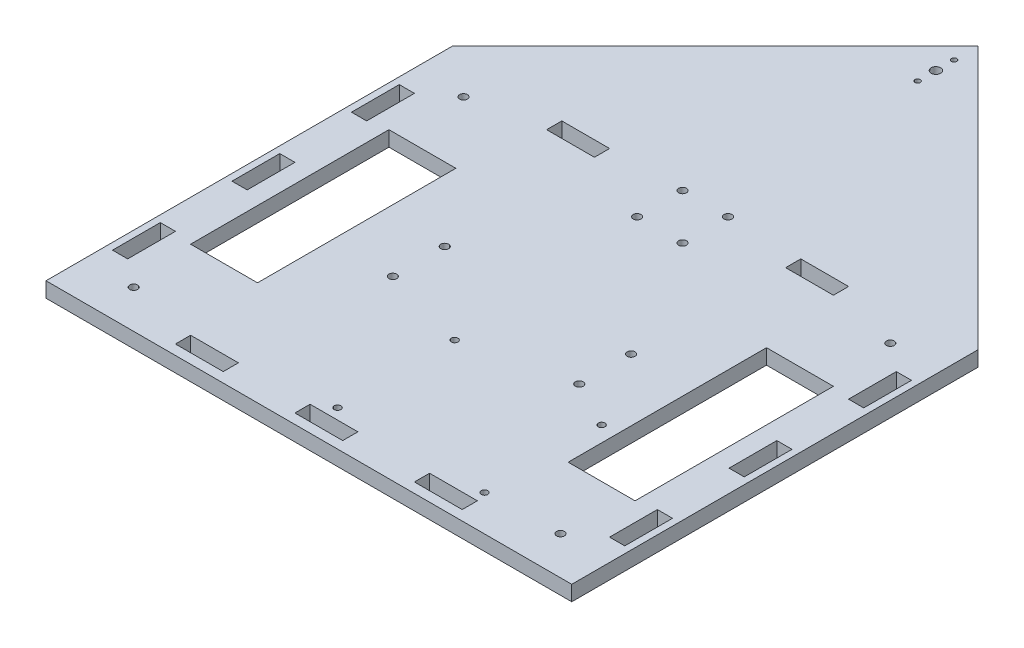
SolidWorks part; units mm, degrees
ref_plane "Front Plane" through (0, 0, 0) normal (0, 0, 1) x (1, 0, 0)
ref_plane "Top Plane" through (0, 0, 0) normal (0, 1, 0) x (1, 0, 0)
ref_plane "Right Plane" through (0, 0, 0) normal (1, 0, 0) x (0, 0, -1)
sketch "Sketch1" plane through (0, 0, 0) normal (0, 1, 0) x (1, 0, 0)
  line L0 (-110, 85) -> (0, 195)
  line L1 (-110, 85) -> (110, 85) construction
  line L2 (-110, 85) -> (-110, -85)
  line L3 (-110, -85) -> (110, -85)
  line L4 (110, 85) -> (110, -85)
  line L5 (-110, 85) -> (110, -85) construction
  line L6 (-110, -85) -> (110, 85) construction
  line L7 (0, 195) -> (110, 85)
  line L8 (0, 85) -> (0, -85) construction
  line L9 (-93, 41.5) -> (-65, 41.5)
  line L10 (-93, 41.5) -> (-93, -41.5)
  line L11 (-93, -41.5) -> (-65, -41.5)
  line L12 (-65, 41.5) -> (-65, -41.5)
  line L13 (-93, 41.5) -> (-65, -41.5) construction
  line L14 (-93, -41.5) -> (-65, 41.5) construction
  line L15 (-110, 0) -> (110, 0) construction
  line L16 (-107.175, 60) -> (-100.825, 60)
  line L17 (-107.175, 10) -> (-100.825, 10)
  line L18 (-107.175, 10) -> (-107.175, -10)
  line L19 (-107.175, -10) -> (-100.825, -10)
  line L20 (-100.825, 10) -> (-100.825, -10)
  line L21 (-107.175, 10) -> (-100.825, -10) construction
  line L22 (-107.175, -10) -> (-100.825, 10) construction
  line L23 (-107.175, 60) -> (-107.175, 40)
  line L24 (-107.175, 40) -> (-100.825, 40)
  line L25 (-100.825, 60) -> (-100.825, 40)
  line L26 (-107.175, 60) -> (-100.825, 40) construction
  line L27 (-107.175, 40) -> (-100.825, 60) construction
  line L28 (-107.175, -40) -> (-100.825, -40)
  line L29 (-107.175, -40) -> (-107.175, -60)
  line L30 (-107.175, -60) -> (-100.825, -60)
  line L31 (-100.825, -40) -> (-100.825, -60)
  line L32 (-107.175, -40) -> (-100.825, -60) construction
  line L33 (-107.175, -60) -> (-100.825, -40) construction
  line L34 (40, -74.4921) -> (60, -74.4921)
  line L35 (-10, -74.4921) -> (10, -74.4921)
  line L36 (-10, -74.4921) -> (-10, -80.8421)
  line L37 (-10, -80.8421) -> (10, -80.8421)
  line L38 (10, -74.4921) -> (10, -80.8421)
  line L39 (-10, -74.4921) -> (10, -80.8421) construction
  line L40 (-10, -80.8421) -> (10, -74.4921) construction
  line L41 (40, -74.4921) -> (40, -80.8421)
  line L42 (40, -80.8421) -> (60, -80.8421)
  line L43 (60, -74.4921) -> (60, -80.8421)
  line L44 (40, -74.4921) -> (60, -80.8421) construction
  line L45 (40, -80.8421) -> (60, -74.4921) construction
  line L46 (-60, -74.4921) -> (-40, -74.4921)
  line L47 (-60, -74.4921) -> (-60, -80.8421)
  line L48 (-60, -80.8421) -> (-40, -80.8421)
  line L49 (-40, -74.4921) -> (-40, -80.8421)
  line L50 (-60, -74.4921) -> (-40, -80.8421) construction
  line L51 (-60, -80.8421) -> (-40, -74.4921) construction
  line L52 (107.175, -60) -> (100.825, -40) construction
  line L53 (107.175, -40) -> (100.825, -60) construction
  line L54 (107.175, 40) -> (100.825, 60) construction
  line L55 (107.175, 60) -> (100.825, 40) construction
  line L56 (107.175, -10) -> (100.825, 10) construction
  line L57 (107.175, 10) -> (100.825, -10) construction
  line L58 (100.825, -40) -> (100.825, -60)
  line L59 (107.175, -60) -> (100.825, -60)
  line L60 (107.175, -40) -> (107.175, -60)
  line L61 (107.175, -40) -> (100.825, -40)
  line L62 (100.825, 60) -> (100.825, 40)
  line L63 (107.175, 40) -> (100.825, 40)
  line L64 (107.175, 60) -> (107.175, 40)
  line L65 (100.825, 10) -> (100.825, -10)
  line L66 (107.175, -10) -> (100.825, -10)
  line L67 (107.175, 10) -> (107.175, -10)
  line L68 (107.175, 10) -> (100.825, 10)
  line L69 (107.175, 60) -> (100.825, 60)
  line L70 (-60, 80.8421) -> (-40, 74.4921) construction
  line L71 (-60, 74.4921) -> (-40, 80.8421) construction
  line L72 (40, 80.8421) -> (60, 74.4921) construction
  line L73 (40, 74.4921) -> (60, 80.8421) construction
  line L76 (-40, 74.4921) -> (-40, 80.8421)
  line L77 (-60, 80.8421) -> (-40, 80.8421)
  line L78 (-60, 74.4921) -> (-60, 80.8421)
  line L79 (-60, 74.4921) -> (-40, 74.4921)
  line L80 (60, 74.4921) -> (60, 80.8421)
  line L81 (40, 80.8421) -> (60, 80.8421)
  line L82 (40, 74.4921) -> (40, 80.8421)
  line L87 (40, 74.4921) -> (60, 74.4921)
  line L88 (93, -41.5) -> (65, 41.5) construction
  line L89 (93, 41.5) -> (65, -41.5) construction
  line L90 (65, 41.5) -> (65, -41.5)
  line L91 (93, -41.5) -> (65, -41.5)
  line L92 (93, 41.5) -> (93, -41.5)
  line L93 (93, 41.5) -> (65, 41.5)
  line L94 (-3, -21) -> (-3, -70) construction
  line L95 (-26.5, -21) -> (58.5, -21) construction
  line L96 (-26.5, -21) -> (-26.5, -70) construction
  line L97 (-26.5, -70) -> (58.5, -70) construction
  line L98 (58.5, -21) -> (58.5, -70) construction
  line L99 (-26.5, -21) -> (58.5, -70) construction
  line L100 (-26.5, -70) -> (58.5, -21) construction
  line L102 (-9.5, 80.875) -> (9.5, 80.875) construction
  line L103 (-9.5, 80.875) -> (-9.5, 61.875) construction
  line L104 (-9.5, 61.875) -> (9.5, 61.875) construction
  line L105 (9.5, 80.875) -> (9.5, 61.875) construction
  line L106 (-9.5, 80.875) -> (9.5, 61.875) construction
  line L107 (-9.5, 61.875) -> (9.5, 80.875) construction
  circle A0 centre (-39, 10.85) radius 1.65
  circle A1 centre (-39, -10.85) radius 1.65
  circle A2 centre (-89.2941, -69) radius 1.65
  circle A3 centre (89.2941, -69) radius 1.65
  circle A4 centre (-89.2941, 69) radius 1.65
  circle A5 centre (89.2941, 69) radius 1.65
  circle A6 centre (39, -10.85) radius 1.65
  circle A7 centre (39, 10.85) radius 1.65
  circle A8 centre (0, 185) radius 1.1
  circle A9 centre (0, 169.75) radius 1.1
  circle A10 centre (-3, -21) radius 1.4
  circle A11 centre (-3, -70) radius 1.4
  circle A12 centre (58.5, -70) radius 1.4
  circle A13 centre (58.5, -21) radius 1.4
  circle A14 centre (-9.5, 80.875) radius 1.65
  circle A15 centre (9.5, 80.875) radius 1.65
  circle A16 centre (9.5, 61.875) radius 1.65
  circle A17 centre (-9.5, 61.875) radius 1.65
  circle A18 centre (0, 177.375) radius 2
  point P0 (0, 0)
  point P6 (-79, 0)
  point P20 (-104, 0)
  point P25 (0, -77.6671)
  point P27 (-104, 50)
  point P32 (-104, -50)
  point P41 (50, -77.6671)
  point P46 (-50, -77.6671)
  point P62 (104, -50)
  point P63 (104, 50)
  point P64 (104, 0)
  point P75 (0, 0)
  point P76 (0, 0)
  point P77 (-50, 77.6671)
  point P78 (50, 77.6671)
  point P79 (11.9394, -45.39)
  point P96 (79, 0)
  point P101 (16, -45.5)
  point P112 (0, 71.375)
  dimension "D6" = 3.3
  dimension "D16" = 3.3
  dimension "D20" = 2.2
  dimension "D25" = 2.8
  dimension "D28" = 3.3
  dimension "D33" = 4
  dimension "D1" = 83
  dimension "D2" = 28
  dimension "D3" = 170
  dimension "D4" = 39
  dimension "D5" = 10.85
  dimension "D7" = 40
  dimension "D8" = 220
  dimension "D9" = 6.35
  dimension "D10" = 20
  dimension "D11" = 6
  dimension "D12" = 2
  dimension "D17" = 16
  dimension "D18" = 110
  dimension "D19" = 15.25
  dimension "D21" = 10
  dimension "D22" = 85
  dimension "D23" = 49
  dimension "D24" = 23.5
  dimension "D26" = 19
  dimension "D27" = 19
  dimension "D29" = 106
  dimension "D31" = 16
  dimension "D32" = 15
  dimension "D34" = 7.625
  dimension "D13" = 2
  dimension "D14" = 2
  dimension "D15" = 2
extrude "Boss-Extrude1" add sketch "Sketch1" along normal blind 6.35
